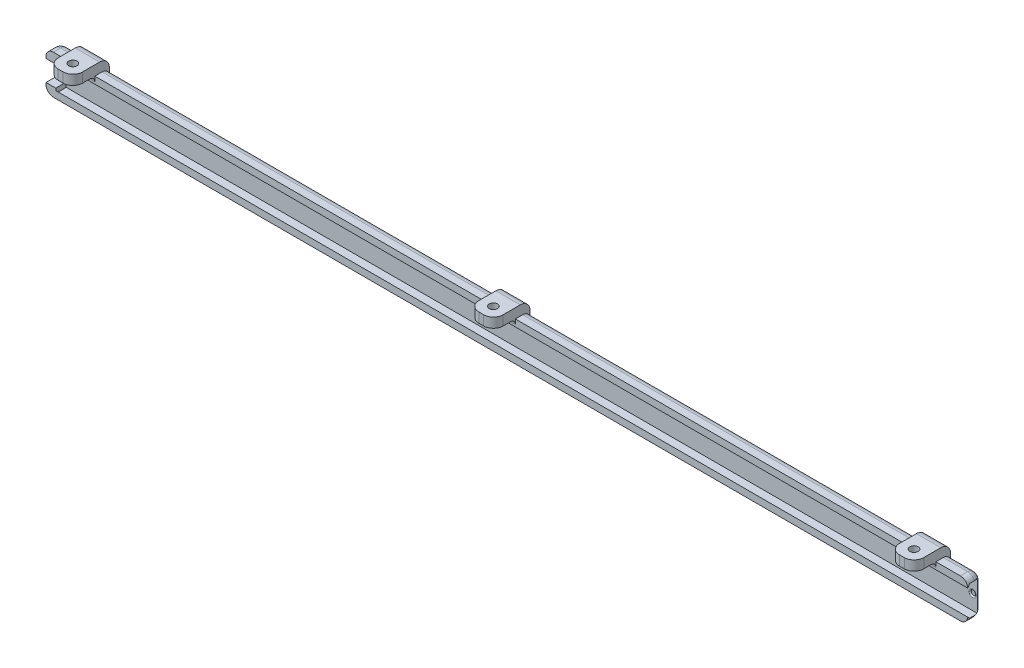
SolidWorks part; units mm, degrees
ref_plane "Front Plane" through (0, 0, 0) normal (0, 0, 1) x (1, 0, 0)
ref_plane "Top Plane" through (0, 0, 0) normal (0, 1, 0) x (1, 0, 0)
ref_plane "Right Plane" through (0, 0, 0) normal (1, 0, 0) x (0, 0, -1)
sketch "Sketch1" plane through (0, 0, 0) normal (0, 0, 1) x (1, 0, 0)
  line L1 (-157.5301, 47.1519) -> (220.4699, 47.1519)
  line L2 (-157.5301, 47.1519) -> (-157.5301, 31.1519)
  line L3 (-157.5301, 31.1519) -> (220.4699, 31.1519)
  line L4 (220.4699, 47.1519) -> (220.4699, 31.1519)
  dimension "D1" = 378
  dimension "D2" = 16
extrude "Boss-Extrude1" add sketch "Sketch1" along normal blind 6
sketch "Sketch3" plane through (220.4699, 0, 0) normal (1, 0, 0) x (0, 0, -1)
  line L0 (-6, 31.1519) -> (-6, 47.1519) construction
  line L1 (-6, 45.3019) -> (-1.7, 45.3019)
  line L2 (-6, 45.3019) -> (-6, 33.0019)
  line L3 (-6, 33.0019) -> (-1.7, 33.0019)
  line L4 (-1.7, 45.3019) -> (-1.7, 33.0019)
  line L5 (-6, 47.1519) -> (0, 47.1519) construction
  dimension "D1" = 12.3
  dimension "D2" = 4.3
  dimension "D3" = 1.85
extrude "Cut-Extrude1" cut sketch "Sketch3" against normal blind 374 and the other way through all
sketch "Sketch4" plane through (220.4699, 0, 0) normal (1, 0, 0) x (0, 0, -1)
  line L0 (-6, 33.0019) -> (-6, 34.0019)
  line L1 (-6, 45.3019) -> (-6, 33.0019) construction
  line L2 (-6, 34.0019) -> (-5, 33.0019)
  line L3 (-6, 33.0019) -> (-1.7, 33.0019) construction
  line L4 (-5, 33.0019) -> (-6, 33.0019)
  dimension "D1" = 1
  dimension "D2" = 1
extrude "Boss-Extrude2" add sketch "Sketch4" against normal blind 374
sketch "Sketch5" plane through (220.4699, 0, 0) normal (1, 0, 0) x (0, 0, -1)
  line L0 (-6, 45.3019) -> (-6, 44.3019)
  line L1 (-6, 45.3019) -> (-6, 34.0019) construction
  line L2 (-6, 44.3019) -> (-5, 45.3019)
  line L3 (-1.7, 45.3019) -> (-6, 45.3019) construction
  line L4 (-5, 45.3019) -> (-6, 45.3019)
  dimension "D1" = 1
  dimension "D2" = 1
extrude "Boss-Extrude3" add sketch "Sketch5" against normal blind 374
sketch "Sketch6" plane through (-153.5301, 0, 0) normal (1, 0, 0) x (0, 0, -1)
  line L0 (-6, 44.3019) -> (-6, 34.0019) construction
  line L1 (-6, 43.4019) -> (-2, 43.4019)
  line L2 (-6, 43.4019) -> (-6, 34.9019)
  line L3 (-6, 34.9019) -> (-2, 34.9019)
  line L4 (-2, 43.4019) -> (-2, 34.9019)
  line L5 (-6, 31.1519) -> (0, 31.1519) construction
  dimension "D1" = 8.5
  dimension "D2" = 3.75
  dimension "D3" = 4
extrude "Cut-Extrude2" cut sketch "Sketch6" against normal through all
fillet "Fillet2" radius 3 1 edges at (-157.5301, 39.1519, 0)
sketch "Sketch13" plane through (0, 47.1519, 0) normal (0, 1, 0) x (1, 0, 0)
  line L0 (220.4699, 0) -> (-154.5301, 0) construction
  line L1 (-137.5301, 0) -> (-147.5301, 0)
  line L2 (-137.5301, 0) -> (-137.5301, -15)
  line L3 (-137.5301, -15) -> (-147.5301, -15)
  line L4 (-147.5301, 0) -> (-147.5301, -15)
  line L5 (-157.5301, -6) -> (-157.5301, -3) construction
  dimension "D1" = 10
  dimension "D2" = 10
  dimension "D3" = 15
extrude "Boss-Extrude5" add sketch "Sketch13" along normal blind 4
fillet "Fillet9" radius 3 3 edges at (-157.5301, 31.1519, 4.5) (-156.6514, 31.1519, 0.8787) (32.9699, 31.1519, 0)
fillet "Fillet10" radius 4 1 edges at (-142.5301, 51.1519, 0)
sketch "Sketch14" plane through (0, 47.1519, 0) normal (0, -1, 0) x (1, 0, 0)
  line L1 (-147.5301, 0) -> (-154.5301, 0) construction
  circle A0 centre (-142.5301, 10) radius 1.7
  dimension "D1" = 3.4
  dimension "D2" = 10
extrude "Cut-Extrude5" cut sketch "Sketch14" against normal blind 4
fillet "Fillet11" radius 4 1 edges at (-137.5301, 49.1519, 15)
fillet "Fillet12" radius 4 1 edges at (-147.5301, 49.1519, 15)
pattern_linear "LPattern3" count 3 spacing 172.5 along (1, 0, 0) of "Boss-Extrude5"
pattern_linear "LPattern4" count 3 spacing 172.5 along (1, 0, 0) of "Cut-Extrude5"
fillet "Fillet13" radius 4 1 edges at (29.9699, 51.1519, 0)
fillet "Fillet14" radius 4 1 edges at (202.4699, 51.1519, 0)
fillet "Fillet15" radius 3 6 edges at (213.9699, 47.1519, 0) (116.2199, 47.1519, 0) (-157.5301, 47.1519, 4.5) (-156.6514, 47.1519, 0.8787) (-151.0301, 47.1519, 0) (-56.2801, 47.1519, 0)
fillet "Fillet16" radius 4 1 edges at (24.9699, 49.1519, 15)
fillet "Fillet17" radius 4 1 edges at (34.9699, 49.1519, 15)
fillet "Fillet18" radius 4 1 edges at (207.4699, 49.1519, 15)
fillet "Fillet19" radius 4 1 edges at (197.4699, 49.1519, 15)
fillet "Fillet20" radius 2 1 edges at (202.4699, 47.1519, 6)
fillet "Fillet21" radius 2 1 edges at (29.9699, 47.1519, 6)
fillet "Fillet22" radius 2 1 edges at (-142.5301, 47.1519, 6)
fillet "Fillet23" radius 3 5 edges at (220.4699, 31.1519, 4.5) (220.4699, 32.0305, 0.8787) (220.4699, 47.1519, 4.5) (220.4699, 46.2732, 0.8787) (220.4699, 39.1519, 0)
sketch "Sketch15" plane through (0, 0, 1.7) normal (0, 0, 1) x (1, 0, 0)
  line L0 (220.1736, 34.1519) -> (220.1736, 44.1519) construction
  line L1 (217.4699, 47.1519) -> (207.4699, 47.1519) construction
  circle A0 centre (218.1736, 39.1519) radius 1
  dimension "D1" = 2
  dimension "D2" = 2
  dimension "D3" = 8
extrude "Cut-Extrude6" cut sketch "Sketch15" against normal blind 0.5
fillet "Fillet24" radius 0.5 1 edges at (219.1736, 39.1519, 1.7)
